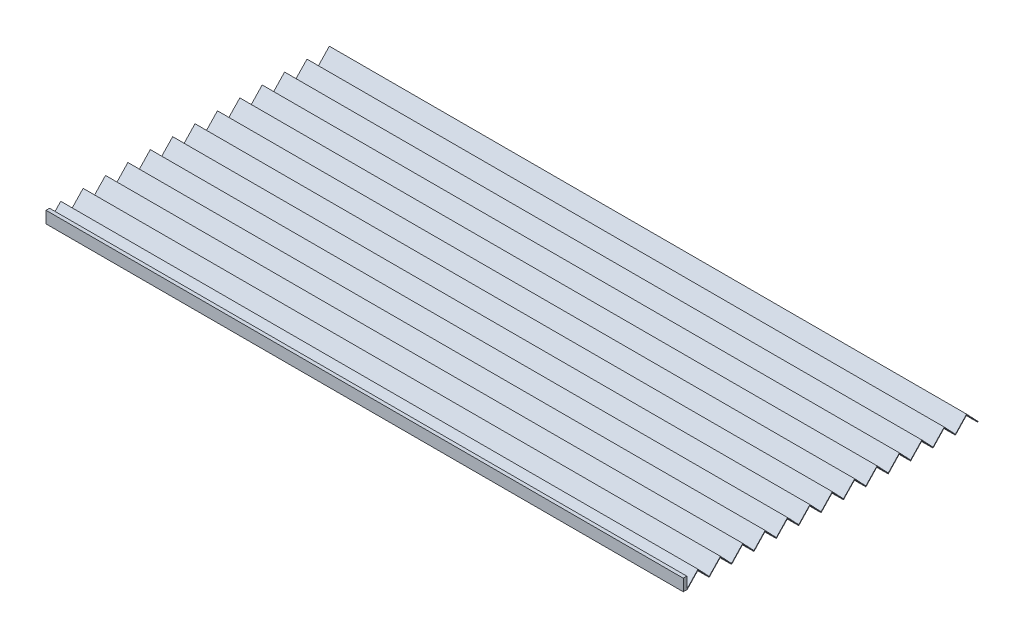
SolidWorks part; units mm, degrees
ref_plane "Front Plane" through (0, 0, 0) normal (0, 0, 1) x (1, 0, 0)
ref_plane "Top Plane" through (0, 0, 0) normal (0, 1, 0) x (1, 0, 0)
ref_plane "Right Plane" through (0, 0, 0) normal (1, 0, 0) x (0, 0, -1)
sketch "Sketch2" plane through (0, 0, 0) normal (0, 0, 1) x (1, 0, 0)
  line L1 (-270, 10) -> (270, 10)
  line L2 (-270, 10) -> (-270, 0)
  line L3 (-270, 0) -> (270, 0)
  line L4 (270, 10) -> (270, 0)
  point P4 (0, 0)
  dimension "D1" = 10
  dimension "D2" = 540
extrude "Boss-Extrude1" add sketch "Sketch2" along normal blind 3
sketch "Sketch3" plane through (270, 0, 0) normal (1, 0, 0) x (0, 0, -1)
  line L0 (0, 10) -> (246.577, 10) construction
  line L1 (0, 0) -> (246.577, 0) construction
  line L2 (246.577, 10) -> (246.577, 0) construction
  line L3 (0, 0) -> (9.4837, 10)
  line L4 (9.4837, 10) -> (18.9675, 0)
  line L5 (18.9675, 0) -> (28.4512, 10)
  line L6 (28.4512, 10) -> (37.9349, 0)
  line L7 (37.9349, 0) -> (47.4187, 10)
  line L8 (47.4187, 10) -> (56.9024, 0)
  line L9 (56.9024, 0) -> (66.3861, 10)
  line L10 (66.3861, 10) -> (75.8699, 0)
  line L11 (75.8699, 0) -> (85.3536, 10)
  line L12 (85.3536, 10) -> (94.8373, 0)
  line L13 (94.8373, 0) -> (104.3211, 10)
  line L14 (104.3211, 10) -> (113.8048, 0)
  line L15 (113.8048, 0) -> (123.2885, 10)
  line L16 (123.2885, 10) -> (132.7723, 0)
  line L17 (132.7723, 0) -> (142.256, 10)
  line L18 (142.256, 10) -> (151.7397, 0)
  line L20 (151.7397, 0) -> (161.2235, 10)
  line L21 (161.2235, 10) -> (170.7072, 0)
  line L22 (170.7072, 0) -> (180.1909, 10)
  line L23 (180.1909, 10) -> (189.6746, 0)
  line L24 (189.6746, 0) -> (199.1584, 10)
  line L25 (199.1584, 10) -> (208.6421, 0)
  line L26 (208.6421, 0) -> (218.1258, 10)
  line L27 (218.1258, 10) -> (227.6096, 0)
  line L28 (227.6096, 0) -> (237.0933, 10)
  line L29 (237.0933, 10) -> (246.577, 0)
  line L30 (246.577, 10) -> (246.577, 0) construction
extrude "Extrude-Thin1" add sketch "Sketch3" against normal through all thin thin type mid plane wall 0.5
